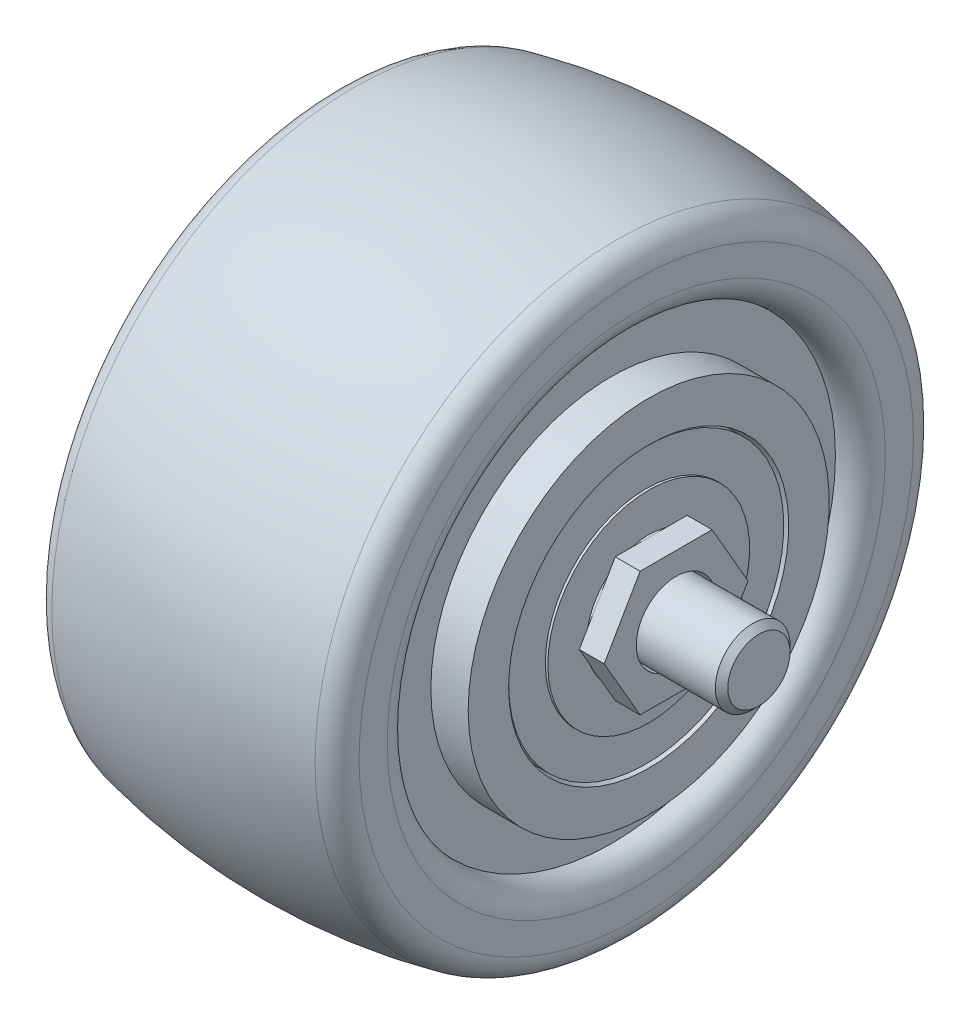
SolidWorks part; units mm, degrees
ref_plane "Front Plane" through (0, 0, 0) normal (0, 0, 1) x (1, 0, 0)
ref_plane "Top Plane" through (0, 0, 0) normal (0, 1, 0) x (1, 0, 0)
ref_plane "Right Plane" through (0, 0, 0) normal (1, 0, 0) x (0, 0, -1)
sketch "Sketch1" plane through (0, 0, 0) normal (1, 0, 0) x (0, 0, -1)
  circle A0 centre (0, 0) radius 25.35
  dimension "D1" = 50.7
extrude "Boss-Extrude1" add sketch "Sketch1" along normal blind 12.15 and the other way blind 12.15
sketch "Sketch2" plane through (0, 0, 0) normal (0, 0, 1) x (1, 0, 0)
  line L0 (0, 0) -> (-48.3586, 0) construction
  line L1 (0, 0) -> (0, -24.65) construction
  line L2 (12.15, 25.35) -> (-12.15, 25.35) construction
  line L4 (15.995, 22.7226) -> (16.3985, 22.7226)
  line L5 (0, 25.35) -> (-8.1733, 25.35) construction
  line L6 (-15.995, 22.7226) -> (-15.995, 31.6473)
  line L7 (-15.995, 31.6473) -> (16.3985, 31.6473)
  line L8 (16.3985, 22.7226) -> (16.3985, 31.6473)
  arc A0 (15.995, 22.7226) -> (-15.995, 22.7226) centre (0, -24.65) ccw
  dimension "D1" = 100
revolve "Cut-Revolve1" cut sketch "Sketch2" angle 360 about L0
fillet "Fillet1" radius 2 2 edges at (-12.15, 0, -23.8513) (12.15, 0, -23.8513)
sketch "Sketch3" plane through (-12.15, 0, 0) normal (-1, 0, 0) x (0, 0, 1)
  circle A0 centre (0, 0) radius 18
  dimension "D1" = 36
extrude "Cut-Extrude1" cut sketch "Sketch3" against normal blind 2
mirror "Mirror1" about plane through (0, 0, 0) normal (1, 0, 0) of "Cut-Extrude1"
fillet "Fillet2" radius 2 2 edges at (-12.15, 0, 18) (12.15, 0, 18)
sketch "Sketch4" plane through (-10.15, 0, 0) normal (-1, 0, 0) x (0, 0, 1)
  circle A0 centre (0, 0) radius 14.5
  dimension "D1" = 29
extrude "Boss-Extrude2" add sketch "Sketch4" along normal blind 3
mirror "Mirror2" about plane through (0, 0, 0) normal (1, 0, 0) of "Boss-Extrude2"
sketch "Sketch5" plane through (-13.15, 0, 0) normal (-1, 0, 0) x (0, 0, 1)
  circle A0 centre (0, 0) radius 11.25
  dimension "D1" = 22.5
extrude "Cut-Extrude2" cut sketch "Sketch5" against normal blind 3
sketch "Sketch6" plane through (-10.15, 0, 0) normal (-1, 0, 0) x (0, 0, 1)
  circle A2 centre (0, 0) radius 11.05
  circle A3 centre (0, 0) radius 11.05
  dimension "D1" = 0.2
extrude "Boss-Extrude3" add sketch "Sketch6" along normal blind 2.8
sketch "Sketch7" plane through (-12.95, 0, 0) normal (-1, 0, 0) x (0, 0, 1)
  circle A0 centre (0, 0) radius 8.1034
extrude "Boss-Extrude4" add sketch "Sketch7" along normal blind 0.2
mirror "Mirror4" about plane through (0, 0, 0) normal (1, 0, 0) of "Boss-Extrude4", "Boss-Extrude3", "Cut-Extrude2"
sketch "Sketch8" plane through (0, 0, 0) normal (1, 0, 0) x (0, 0, -1)
  circle A0 centre (0, 0) radius 3
  dimension "D1" = 6
extrude "Boss-Extrude5" add sketch "Sketch8" along normal blind 22 and the other way blind 22
chamfer "Chamfer1" distance 0.5 angle 45 2 edges at (22, 0, -3) (-22, 0, -3)
sketch "Sketch9" plane through (-13.15, 0, 0) normal (-1, 0, 0) x (0, 0, 1)
  circle A0 centre (0, 0) radius 5
  circle A1 centre (0, 0) radius 3
  dimension "D1" = 10
extrude "Boss-Extrude6" add sketch "Sketch9" along normal blind 0.2
mirror "Mirror5" about plane through (0, 0, 0) normal (1, 0, 0) of "Boss-Extrude6"
sketch "Sketch10" plane through (13.35, 0, 0) normal (1, 0, 0) x (0, 0, -1)
  line L1 (5.7735, 0) -> (2.8868, 5)
  line L2 (2.8868, 5) -> (-2.8868, 5)
  line L3 (-2.8868, 5) -> (-5.7735, 0)
  line L4 (-5.7735, 0) -> (-2.8868, -5)
  line L5 (-2.8868, -5) -> (2.8868, -5)
  line L6 (2.8868, -5) -> (5.7735, 0)
  circle A0 centre (0, 0) radius 5 construction
  circle A1 centre (0, 0) radius 3.2
  dimension "D2" = 6.4
  dimension "D1" = 10
extrude "Boss-Extrude7" add sketch "Sketch10" along normal blind 2
mirror "Mirror6" about plane through (0, 0, 0) normal (1, 0, 0) of "Boss-Extrude7"
